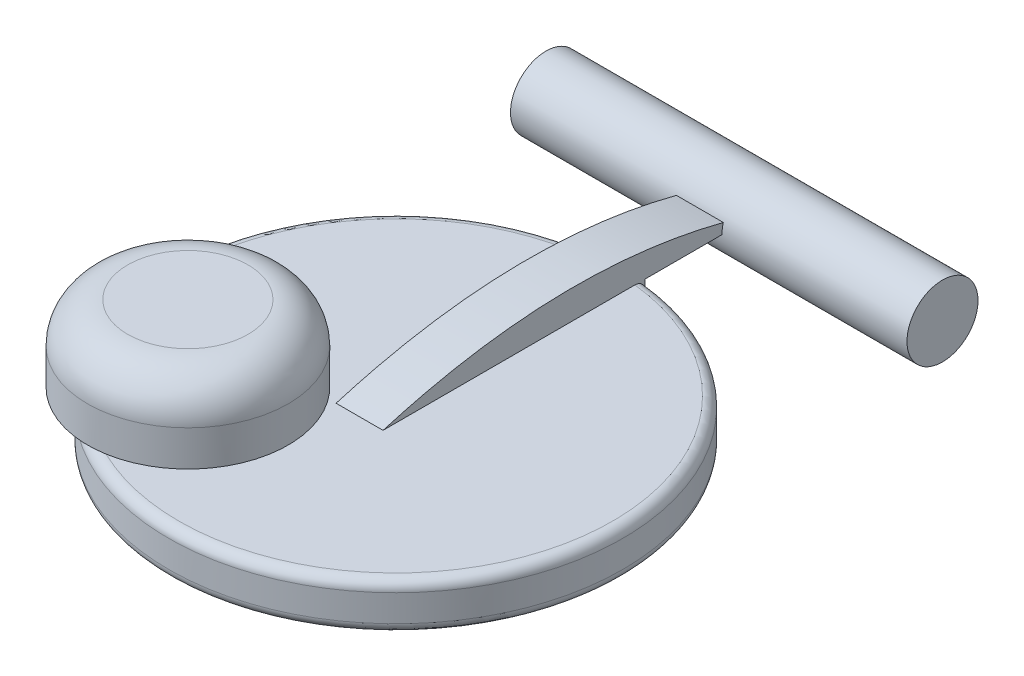
SolidWorks part; units mm, degrees
material "6061 Alloy"
ref_plane "Front Plane" through (0, 0, 0) normal (0, 0, 1) x (1, 0, 0)
ref_plane "Top Plane" through (0, 0, 0) normal (0, 1, 0) x (1, 0, 0)
ref_plane "Right Plane" through (0, 0, 0) normal (1, 0, 0) x (0, 0, -1)
sketch "Sketch1" plane through (0, 0, 0) normal (1, 0, 0) x (0, 0, -1)
  circle A0 centre (0, 0) radius 2.2479
  dimension "D1" = 4.4958
extrude "Boss-Extrude1" add sketch "Sketch1" along normal blind 25.0952
ref_plane "Plane1" through (10.414, 0, 0) normal (1, 0, 0) x (0, 0, -1)
sketch "Sketch2" plane through (10.414, 0, 0) normal (1, 0, 0) x (0, 0, -1)
  line L0 (0, 0) -> (-23.6982, 0)
  line L1 (2.4727, 0) -> (-2.4727, 0) construction
  spline S0 degree 2 poles (0, 0) (-11.4154, 3.6607) (-23.6982, 0) knots 0 0 0 1 1 1
  point P7 (-2.7949, 0.7834)
  point P8 (0, 0)
  dimension "D1" = 23.6982
extrude "Boss-Extrude2" add sketch "Sketch2" along normal blind 2.9718
sketch "Sketch3" plane through (0, 0, 0) normal (0, -1, 0) x (1, 0, 0)
  line L0 (11.8999, 23.6982) -> (11.8999, 2.2479) construction
  line L1 (13.3858, 23.6982) -> (10.414, 23.6982) construction
  line L2 (10.414, 2.2479) -> (13.3858, 2.2479) construction
  circle A0 centre (11.8999, 21.4057) radius 14.3637
  dimension "D1" = 2.2925
  dimension "D2" = 28.7274
extrude "Boss-Extrude3" add sketch "Sketch3" along normal blind 2.9718
fillet "Fillet1" radius 0.635 2 edges at (11.8999, -2.9718, 7.042) (11.8999, 0, 35.7694)
sketch "Sketch4" plane through (0, 0, 0) normal (0, 1, 0) x (1, 0, 0)
  line L0 (10.414, -23.6982) -> (10.414, -7.7577) construction
  line L1 (13.3858, -23.6982) -> (10.414, -23.6982) construction
  circle A0 centre (4.8442, -27.5082) radius 6.35
  point P2 (0, 0)
  point P3 (4.8442, -26.1587)
  dimension "D1" = 12.7
  dimension "D2" = 5.5698
  dimension "D3" = 3.81
extrude "Boss-Extrude4" add sketch "Sketch4" along normal blind 4.8006
fillet "Fillet2" radius 2.54 1 edges at (4.8442, 4.8006, 33.8582)
